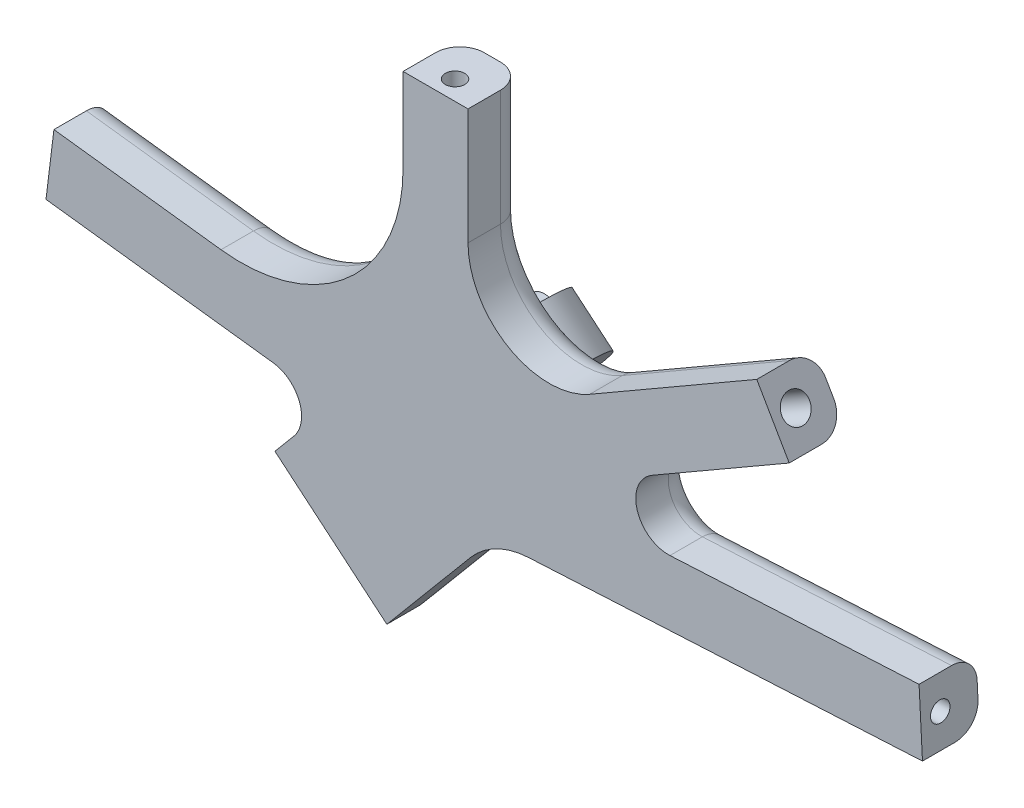
SolidWorks part; units mm, degrees
ref_plane "前基準面" through (0, 0, 0) normal (0, 0, 1) x (1, 0, 0)
ref_plane "上基準面" through (0, 0, 0) normal (0, 1, 0) x (1, 0, 0)
ref_plane "右基準面" through (0, 0, 0) normal (1, 0, 0) x (0, 0, -1)
sketch "草圖1" plane through (0, 0, 0) normal (0, 0, 1) x (1, 0, 0)
  line L0 (-27, 0) -> (-10.1968, 0) construction
  line L1 (-27, 3.1712) -> (-9.3539, 1.0045)
  line L2 (0.5569, -1.1858) -> (27, 0.2)
  line L3 (-27, 3.1712) -> (-26.5125, 7.1414)
  line L4 (-26.5125, 7.1414) -> (-5, 4.5)
  line L5 (3.1228, 2.9541) -> (26.7907, 4.1945)
  line L6 (26.7907, 4.1945) -> (27, 0.2)
  line L7 (-1, 5.1927) -> (16.7907, 15.4641)
  line L8 (16.7907, 15.4641) -> (18.7907, 12)
  line L9 (18.7907, 12) -> (3.1228, 2.9541)
  line L10 (-5, 4.5) -> (-5, 21)
  line L11 (-5, 21) -> (-1, 21)
  line L12 (-1, 21) -> (-1, 5.1927)
  line L13 (-9.3539, 1.0045) -> (-12.8944, -3.2149)
  line L14 (-12.8944, -3.2149) -> (-6, -9)
  line L15 (-6, -9) -> (0.5569, -1.1858)
  line L17 (1.5519, 0) -> (27, 0) construction
  point P19 (-10.1968, 0)
  dimension "D1" = 54
  dimension "D2" = 27
  dimension "D3" = 7
  dimension "D4" = 3
  dimension "D5" = 90
  dimension "D6" = 4
  dimension "D7" = 4
  dimension "D8" = 4.5
  dimension "D9" = 4
  dimension "D10" = 30
  dimension "D11" = 8
  dimension "D12" = 12
  dimension "D13" = 4
  dimension "D14" = 22
  dimension "D15" = 130
  dimension "D16" = 90
  dimension "D17" = 9
  dimension "D18" = 21
  dimension "D19" = 16.5
  dimension "D20" = 0.2
  dimension "D21" = 9
extrude "填料-伸長1" add sketch "草圖1" along normal blind 3.5
fillet "圓角1" radius 5 2 edges at (0.5569, -1.1858, 1.75) (-1, 5.1927, 1.75)
fillet "圓角2" radius 2 2 edges at (-9.3539, 1.0045, 1.75) (3.1228, 2.9541, 1.75)
fillet "圓角3" radius 10 1 edges at (-5, 4.5, 1.75)
sketch "草圖2" plane through (-26.9826, 3.313, 0) normal (-0.9925, 0.1219, 0) x (0, 0, 1)
  line L0 (3.5, 3.8571) -> (0, 3.8571) construction
  line L1 (3.5, 3.8571) -> (3.5, -0.1429) construction
  circle A0 centre (2.3, 1.8571) radius 0.6
  dimension "D1" = 1.2
  dimension "D2" = 2
  dimension "D3" = 1.2
extrude "除料-伸長1" cut sketch "草圖2" against normal blind 20
sketch "草圖3" plane through (0, 21, 0) normal (0, 1, 0) x (1, 0, 0)
  line L0 (-1, -3.5) -> (-1, 0) construction
  line L1 (-1, -3.5) -> (-5, -3.5) construction
  circle A0 centre (-3, -2.3) radius 0.6
  dimension "D2" = 1.2
  dimension "D1" = 2
  dimension "D3" = 1.2
extrude "除料-伸長2" cut sketch "草圖3" against normal blind 15
sketch "草圖4" plane through (19.2891, 11.1366, 0) normal (0.866, 0.5, 0) x (0, 0, -1)
  line L0 (-3.5, 4.997) -> (0, 4.997) construction
  line L1 (-3.5, 0.997) -> (-3.5, 4.997) construction
  circle A0 centre (-2.1, 2.997) radius 0.85
  point P2 (-1.75, 4.997)
  dimension "D2" = 1.7
  dimension "D1" = 2
  dimension "D3" = 1.4
extrude "除料-伸長3" cut sketch "草圖4" against normal blind 15
sketch "草圖5" plane through (26.9365, 1.4117, 0) normal (0.9986, 0.0523, 0) x (0, 0, -1)
  line L0 (0, 2.7867) -> (-3.5, 2.7867) construction
  line L1 (-3.5, -1.2133) -> (-3.5, 2.7867) construction
  circle A0 centre (-2.3, 0.7867) radius 0.6
  dimension "D2" = 1.2
  dimension "D1" = 2
  dimension "D3" = 1.2
extrude "除料-伸長4" cut sketch "草圖5" against normal blind 20
sketch "草圖6" plane through (0, 0, 0) normal (0, 0, -1) x (-1, 0, 0)
  line L0 (9.4472, -6.1075) -> (11.9751, -3.9863)
  line L1 (12.8944, -3.2149) -> (6, -9) construction
  line L2 (11.9751, -3.9863) -> (4.2617, 5.2063)
  line L3 (4.2617, 5.2063) -> (1.7337, 3.0851)
  line L4 (1.7337, 3.0851) -> (9.4472, -6.1075)
  line L5 (9.4472, -6.1075) -> (9.175, -6.0253)
  line L6 (6, -9) -> (0.8406, -2.8513) construction
  line M17 (6, -9) -> (12.8944, -3.2149)
  dimension "D1" = 3.3
  dimension "D2" = 12
extrude "填料-伸長2" add sketch "草圖6" along normal blind 8 contours L3 L4 L2 M17 region at (-6.8544, -0.4506, 0)
sketch "草圖7" plane through (-2.5365, 2.1284, 0) normal (0.766, -0.6428, 0) x (0, 0, -1)
  line L0 (8, -10.7511) -> (0, -10.7511) construction
  circle A0 centre (4, -8.7511) radius 1
  circle A2 centre (4, -0.7511) radius 1
  dimension "D1" = 2
  dimension "D6" = 2
  dimension "D2" = 2
  dimension "D3" = 4
  dimension "D4" = 8
extrude "除料-伸長6" cut sketch "草圖7" against normal up to next
fillet "圓角4" radius 4 1 edges at (-2.9977, 4.1457, -8)
sketch "草圖8" plane through (-5.0645, 4.2496, 0) normal (-0.766, 0.6428, 0) x (0, 0, 1)
  circle A0 centre (-4, -0.7511) radius 1.8
  circle A1 centre (-4, -8.7511) radius 1.8
  dimension "D1" = 3.6
  dimension "D2" = 3.6
extrude "除料-伸長7" cut sketch "草圖8" against normal blind 0.5
fillet "圓角5" radius 1.5 15 edges at (-12.308, -2.5161, 0) (-11.3928, 0.2014, 0) (-21.3656, 6.5094, 0) (-5, 18.4015, 0) (-1, 17.4265, 0) (1.5, 9.5228, 0) (14.564, 9.5597, 0) (9.4196, 4.8194, 0) (-3.4203, -5.9256, 0) (0.7586, -1.5905, 0) (-20.005, 2.3123, 0) (-8.3738, 8.3134, 0) (11.6453, 12.4934, 0) (19.1163, 3.7923, 0) (14.864, -0.436, 0)
sketch "草圖9" plane through (-5.0645, 4.2496, 0) normal (-0.766, 0.6428, 0) x (0, 0, 1)
  line L0 (-8, -10.7511) -> (-8, -2.7511) construction
  line L1 (-8, -3.2511) -> (0, -3.2511)
  line L2 (-8, -3.2511) -> (-8, -6.2511)
  line L3 (-8, -6.2511) -> (0, -6.2511)
  line L4 (0, -3.2511) -> (0, -6.2511)
  line L5 (0, -7.5088) -> (0, 1.2489) construction
  circle A0 centre (-4, -0.7511) radius 1 construction
  circle A1 centre (-4, -8.7511) radius 1 construction
  dimension "D1" = 2.5
  dimension "D2" = 2.5
extrude "填料-伸長3" add sketch "草圖9" along normal blind 1
fillet "圓角6" radius 1 2 edges at (-9.8486, 0.1037, -4) (-7.9203, 2.4019, -4)
